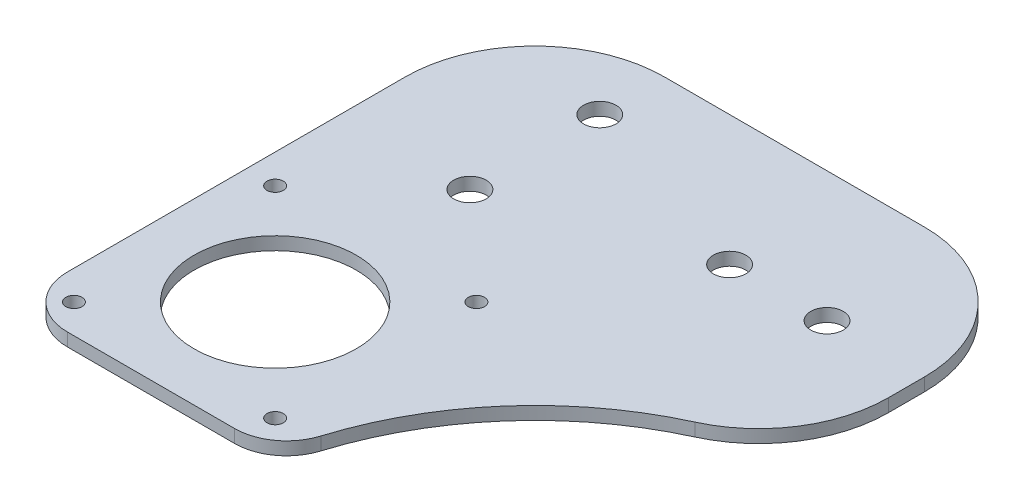
SolidWorks part; units mm, degrees
ref_plane "Plan de face" through (0, 0, 0) normal (0, 0, 1) x (1, 0, 0)
ref_plane "Plan de dessus" through (0, 0, 0) normal (0, 1, 0) x (1, 0, 0)
ref_plane "Plan de droite" through (0, 0, 0) normal (1, 0, 0) x (0, 0, -1)
sketch "Sketch1" plane through (0, 0, 0) normal (0, 1, 0) x (1, 0, 0)
  line L0 (4.5, -4.5) -> (35.5, -4.5) construction
  line L1 (80, 40) -> (0, 40)
  line L2 (80, 40) -> (80, 0)
  line L3 (80, 0) -> (0, 0)
  line L4 (0, 40) -> (0, 0)
  line L5 (0, 0) -> (40, 0)
  line L6 (0, 0) -> (0, -40)
  line L7 (0, -40) -> (40, -40)
  line L8 (40, 0) -> (40, -40)
  line L9 (4.5, -4.5) -> (4.5, -35.5) construction
  line L10 (4.5, -35.5) -> (35.5, -35.5) construction
  line L11 (35.5, -4.5) -> (35.5, -35.5) construction
  circle A0 centre (20, 10) radius 2.5
  circle A1 centre (65, 20) radius 2.5
  circle A2 centre (50, 20) radius 2.5
  circle A3 centre (20, 30) radius 2.5
  circle A4 centre (4.5, -4.5) radius 1.25
  circle A5 centre (35.5, -4.5) radius 1.25
  circle A6 centre (35.5, -35.5) radius 1.25
  circle A7 centre (4.5, -35.5) radius 1.25
  circle A8 centre (20, -20) radius 12.5
  point P15 (0, 20)
  point P27 (20, -4.5)
  point P30 (20, -40)
  point P32 (0, -20)
  point P33 (4.5, -20)
  point P35 (20, -35.5)
  dimension "D3" = 5
  dimension "D4" = 5
  dimension "D5" = 5
  dimension "D9" = 5
  dimension "D14" = 25
  dimension "D1" = 40
  dimension "D2" = 80
  dimension "D6" = 20
  dimension "D7" = 10
  dimension "D8" = 15
  dimension "D10" = 10
  dimension "D12" = 40
  dimension "D13" = 40
  dimension "D15" = 31
  dimension "D16" = 31
extrude "Boss-Extrude1" add sketch "Sketch1" along normal blind 2 contours L1 L4 L3 L2 A3 A2 A1 A0 | L8 L3 L6 L7 region at (40.0315, 0, -20) region at (20, 0, 0.5657)
fillet "Fillet1" radius 50 1 edges at (40, 1, 0)
fillet "Fillet2" radius 20 3 edges at (80, 1, -40) (80, 1, 0) (0, 1, -40)
fillet "Fillet3" radius 8 2 edges at (0, 1, 40) (40, 1, 40)
